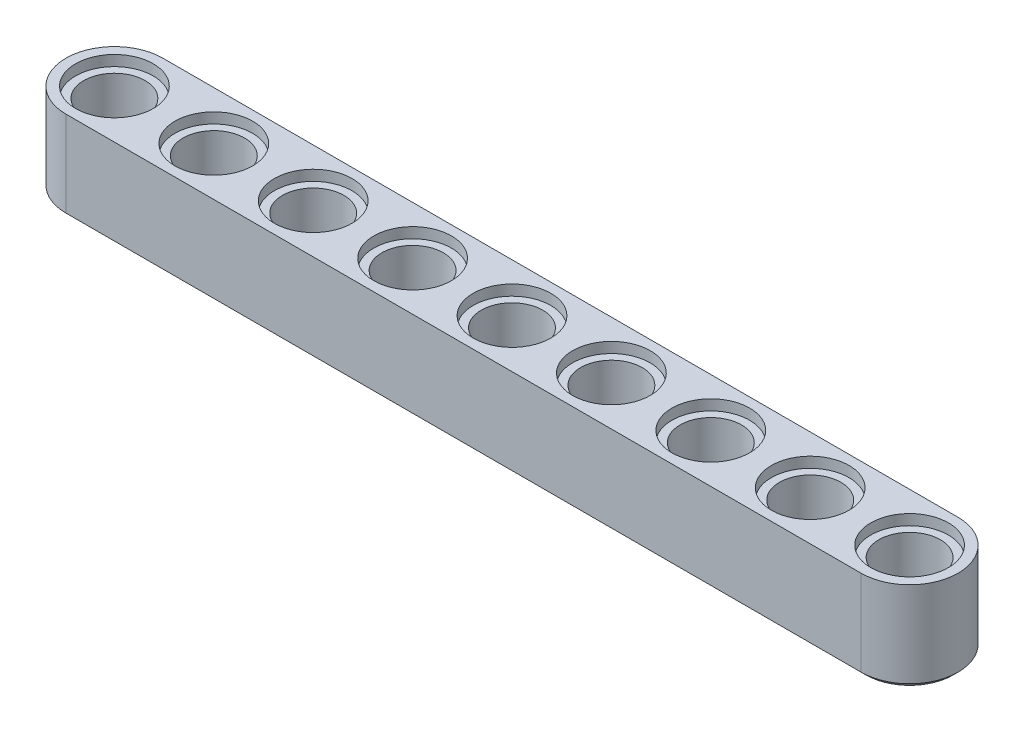
SolidWorks part; units mm, degrees
ref_plane "Front Plane" through (0, 0, 0) normal (0, 0, 1) x (1, 0, 0)
ref_plane "Top Plane" through (0, 0, 0) normal (0, 1, 0) x (1, 0, 0)
ref_plane "Right Plane" through (0, 0, 0) normal (1, 0, 0) x (0, 0, -1)
sketch "Sketch1" plane through (0, 0, 0) normal (0, 1, 0) x (1, 0, 0)
  line L0 (0, 0) -> (64, 0) construction
  line L1 (0, 3.9) -> (64, 3.9)
  line L2 (0, -3.9) -> (64, -3.9)
  arc A0 (0, 3.9) -> (0, -3.9) centre (0, 0) ccw
  arc A1 (64, -3.9) -> (64, 3.9) centre (64, 0) ccw
  point P3 (32, 0)
  dimension "D1" = 64
  dimension "D2" = 7.8
extrude "Boss-Extrude1" add sketch "Sketch1" along normal blind 7.3
sketch "Sketch2" plane through (0, 7.3, 0) normal (0, 1, 0) x (1, 0, 0)
  circle A0 centre (0, 0) radius 2.475
  dimension "D1" = 4.95
extrude "Cut-Extrude1" cut sketch "Sketch2" against normal through all
sketch "Sketch3" plane through (0, 7.3, 0) normal (0, 1, 0) x (1, 0, 0)
  circle A0 centre (0, 0) radius 3.125
  dimension "D1" = 6.25
extrude "Cut-Extrude2" cut sketch "Sketch3" against normal blind 0.85
ref_plane "Plane1" through (0, 3.65, 0) normal (0, 1, 0) x (1, 0, 0)
mirror "Mirror1" about plane through (0, 3.65, 0) normal (0, 1, 0) of "Cut-Extrude2"
pattern_linear "LPattern1" count 9 spacing 8 along (1, 0, 0) of "Cut-Extrude1", "Cut-Extrude2", "Mirror1"
chamfer "Chamfer1" distance 0.4 angle 45 13 edges at (32, 0, 3.9) (67.9, 0, 0) (32, 0, -3.9) (-3.9, 0, 0) (0, 0, 3.125) (8, 0, 3.125) (16, 0, 3.125) (24, 0, 3.125) (32, 0, 3.125) (40, 0, 3.125) (48, 0, 3.125) (56, 0, 3.125) (64, 0, 3.125)
equation "\"Pitch\"= 8"
equation "\"Beam_Height\"= 7.8"
equation "\"Beam_Width\"= 7.3"
equation "\"Pin_Hole_Dia\"= 4.95"
equation "\"CBore_Dia\"= 6.25"
equation "\"CBore_Depth\"= 0.85"
equation "\"D2@Sketch1\"=\"Beam_Height\""
equation "\"D1@Boss-Extrude1\"=\"Beam_Width\""
equation "\"D1@Sketch2\"=\"Pin_Hole_Dia\""
equation "\"D1@Sketch3\"=\"CBore_Dia\""
equation "\"D1@Cut-Extrude2\"=\"CBore_Depth\""
equation "\"D3@LPattern1\"=\"Pitch\""
